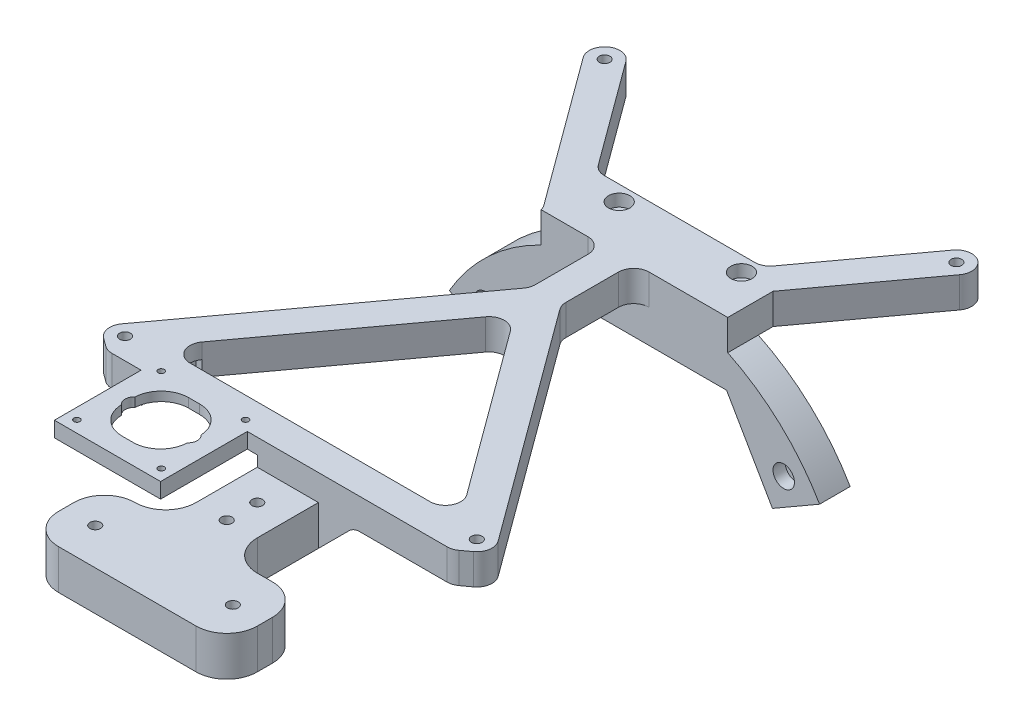
SolidWorks part; units mm, degrees
ref_plane "Plan de face" through (0, 0, 0) normal (0, 0, 1) x (1, 0, 0)
ref_plane "Plan de dessus" through (0, 0, 0) normal (0, 1, 0) x (1, 0, 0)
ref_plane "Plan de droite" through (0, 0, 0) normal (1, 0, 0) x (0, 0, -1)
sketch "Esquisse1" plane through (0, 0, 0) normal (0, 0, 1) x (1, 0, 0)
  line L0 (-30.13, 52.18) -> (30.13, 52.18)
  line L1 (30.13, 52.18) -> (45.13, 26.1992)
  line L2 (45.13, 26.1992) -> (60.5596, 35.1075)
  line L3 (-30.13, 52.18) -> (-45.13, 26.1992)
  line L4 (-45.13, 26.1992) -> (-60.5596, 35.1075)
  line L5 (-30.5123, 63) -> (30.5123, 63)
  circle A0 centre (0, 0) radius 70 construction
  arc A1 (-60.5596, 35.1075) -> (-30.5123, 63) centre (0, 0) cw
  arc A2 (60.5596, 35.1075) -> (30.5123, 63) centre (0, 0) ccw
  point P5 (0, 52.18)
  point P12 (0, 63)
  dimension "D1" = 140
  dimension "D2" = 120
  dimension "D3" = 30
  dimension "D4" = 60.26
  dimension "D5" = 61.0246
  dimension "D6" = 10.82
extrude "Boss.-Extru.1" add sketch "Esquisse1" along normal blind 10
sketch "Esquisse2" plane through (0, 63, 0) normal (0, 1, 0) x (1, 0, 0)
  line L0 (-30.5123, -10) -> (-30.5123, 0) construction
  line L1 (30.5123, -10) -> (-30.5123, -10)
  line L2 (30.5123, -10) -> (30.5123, 10)
  line L3 (30.5123, 10) -> (-30.5123, 10)
  line L4 (-30.5123, -10) -> (-30.5123, 10)
  line L5 (30.5123, 0) -> (-30.5123, 0) construction
  dimension "D1" = 10
extrude "Boss.-Extru.2" add sketch "Esquisse2" along normal blind 10
sketch "Esquisse5" plane through (0, 0, 10) normal (0, 0, 1) x (1, 0, 0)
  line L0 (-41.2992, 32.8344) -> (-56.3527, 41.5256) construction
  line L1 (-45.13, 26.1992) -> (-30.13, 52.18) construction
  line L2 (41.2992, 32.8344) -> (56.3527, 41.5256) construction
  line L3 (30.13, 52.18) -> (45.13, 26.1992) construction
  line L4 (-48.8259, 37.18) -> (48.8259, 37.18) construction
  line L5 (0, 52.18) -> (0, 37.18) construction
  line L6 (-30.13, 52.18) -> (30.13, 52.18) construction
  line L7 (-60.5596, 35.1075) -> (-45.13, 26.1992) construction
  line L8 (45.13, 26.1992) -> (60.5596, 35.1075) construction
  arc A0 (-30.5123, 63) -> (-60.5596, 35.1075) centre (0, 0) ccw construction
  arc A1 (60.5596, 35.1075) -> (30.5123, 63) centre (0, 0) ccw construction
  circle A2 centre (-48.8259, 37.18) radius 1.75
  circle A3 centre (48.8259, 37.18) radius 1.75
  dimension "D2" = 3.5
  dimension "D1" = 15
extrude "Enlèv. mat.-Extru.3" cut sketch "Esquisse5" against normal up to next
sketch "Esquisse3" plane through (0, 73, 0) normal (0, 1, 0) x (1, 0, 0)
  line L0 (30.5123, 0) -> (-30.5123, 0) construction
  line L1 (30.5123, -10) -> (30.5123, 10) construction
  line L2 (-30.5123, 10) -> (-30.5123, -10) construction
  line L3 (0, 0) -> (0, 10) construction
  line L4 (30.5123, 10) -> (-30.5123, 10) construction
  line L5 (20, 5) -> (-20, 5) construction
  circle A0 centre (20, 5) radius 1.75
  circle A1 centre (-20, 5) radius 1.75
  point P14 (0, 5)
  point P15 (0, 5)
  dimension "D1" = 3.5
  dimension "D2" = 20
extrude "Enlèv. mat.-Extru.1" cut sketch "Esquisse3" against normal up to next
sketch "Esquisse4" plane through (0, 73, 0) normal (0, 1, 0) x (1, 0, 0)
  circle A0 centre (20, 5) radius 3.5
  circle A1 centre (-20, 5) radius 3.5
  dimension "D1" = 7
extrude "Enlèv. mat.-Extru.2" cut sketch "Esquisse4" against normal blind 4
sketch "Esquisse6" plane through (0, 0, 10) normal (0, 0, 1) x (1, 0, 0)
  circle A0 centre (-48.8259, 37.18) radius 3.5
  circle A1 centre (48.8259, 37.18) radius 3.5
  dimension "D1" = 7
extrude "Enlèv. mat.-Extru.4" cut sketch "Esquisse6" against normal blind 4
sketch "Esquisse7" plane through (0, 73, 0) normal (0, 1, 0) x (1, 0, 0)
  line L0 (0, -10) -> (0, 10) construction
  line L1 (-30.5123, -10) -> (30.5123, -10) construction
  line L2 (30.5123, 10) -> (-30.5123, 10) construction
  line L3 (-62.77, -113.9) -> (52.31, 43) construction
  line L4 (52.31, -113.9) -> (-62.77, 43) construction
  line L5 (-10.23, -10) -> (-10.23, -33.8129)
  line L7 (59.2989, -114.9746) -> (51.2354, -120.8889)
  line L8 (51.2354, -120.8889) -> (-5.23, -43.9041)
  line L9 (-5.23, -43.9041) -> (-61.6954, -120.8889)
  line L10 (-61.6954, -120.8889) -> (-69.7589, -114.9746)
  line L12 (-0.23, -33.8129) -> (-0.23, -10)
  line L13 (52.31, -113.9) -> (55.2672, -117.9318) construction
  line L14 (-62.77, -113.9) -> (-65.7272, -117.9318) construction
  line L16 (30.5123, 4.8269) -> (59.2989, 44.0746)
  line L17 (59.2989, 44.0746) -> (51.2354, 49.9889)
  line L18 (51.2354, 49.9889) -> (21.9051, 10)
  line L19 (52.31, 43) -> (55.2672, 47.0318) construction
  line L20 (-32.3651, 10) -> (-61.6954, 49.9889)
  line L21 (-61.6954, 49.9889) -> (-69.7589, 44.0746)
  line L22 (-69.7589, 44.0746) -> (-30.5123, -9.4342)
  line L23 (-30.5123, 10) -> (-30.5123, -10) construction
  line L24 (-30.5123, -9.4342) -> (-30.5123, 10)
  line L25 (-30.5123, 10) -> (-32.3651, 10)
  line L26 (-62.77, 43) -> (-65.7272, 47.0318) construction
  line L27 (-10.23, -10) -> (-0.23, -10)
  line L28 (30.5123, 10) -> (30.5123, 4.8269)
  line L29 (30.5123, -10) -> (30.5123, 10) construction
  line L30 (30.5123, 10) -> (21.9051, 10)
  line L31 (59.2989, -114.9746) -> (-0.23, -33.8129)
  line L32 (-10.23, -33.8129) -> (-69.7589, -114.9746)
  circle A0 centre (52.31, -113.9) radius 1.75
  circle A1 centre (-62.77, -113.9) radius 1.75
  circle A2 centre (-62.77, 43) radius 1.75
  circle A3 centre (52.31, 43) radius 1.75
  point P10 (-5.23, -35.45)
  point P11 (-5.23, -35.45)
  dimension "D5" = 3.5
  dimension "D1" = 156.9
  dimension "D2" = 115.08
  dimension "D3" = 5.23
  dimension "D4" = 5
  dimension "D6" = 10
  dimension "D8" = 33
extrude "Boss.-Extru.3" add sketch "Esquisse7" against normal up to surface (10 mm away) up to face at (20, 63, -3.25)
sketch "Esquisse8" plane through (0, 73, 0) normal (0, 1, 0) x (1, 0, 0)
  line L0 (51.2354, -120.8889) -> (43.9008, -110.8889)
  line L1 (-5.23, -43.9041) -> (51.2354, -120.8889) construction
  line L2 (43.9008, -110.8889) -> (-54.3608, -110.8889)
  line L3 (-61.6954, -120.8889) -> (-5.23, -43.9041) construction
  line L4 (-54.3608, -110.8889) -> (-61.6954, -120.8889)
  line L5 (-61.6954, -120.8889) -> (51.2354, -120.8889)
  dimension "D1" = 10
extrude "Boss.-Extru.4" add sketch "Esquisse8" against normal up to surface (10 mm away) up to face at (-5.23, 63, 67.0286)
ref_plane "Plan1" through (0, 64.5, 0) normal (0, -1, 0) x (-1, 0, 0)
sketch "Esquisse9" plane through (0, 63, 0) normal (0, -1, 0) x (-1, 0, 0)
  circle A0 centre (-52.31, -113.9) radius 3.5
  circle A1 centre (62.77, -113.9) radius 3.5
  circle A2 centre (62.77, 43) radius 3.5
  circle A3 centre (-52.31, 43) radius 3.5
  dimension "D1" = 7
extrude "Enlèv. mat.-Extru.5" cut sketch "Esquisse9" against normal blind 3
sketch "Esquisse10" plane through (0, 64.5, 0) normal (0, -1, 0) x (-1, 0, 0)
  line L0 (54.3608, -110.8889) -> (-43.9008, -110.8889) construction
  line L1 (32.5, -175.8889) -> (-32.5, -175.8889)
  line L5 (-51.2354, -120.8889) -> (61.6954, -120.8889) construction
  line L6 (32.5, -150.8889) -> (12.5, -150.8889)
  line L7 (12.5, -150.8889) -> (12.5, -110.8889)
  line L8 (12.5, -110.8889) -> (-7.5, -110.8889)
  line L9 (-7.5, -110.8889) -> (-7.5, -150.8889)
  line L10 (-7.5, -150.8889) -> (-32.5, -150.8889)
  line L11 (32.5, -175.8889) -> (32.5, -150.8889)
  line L12 (-32.5, -175.8889) -> (-32.5, -150.8889)
  dimension "D3" = 49.1954
  dimension "D1" = 65
  dimension "D2" = 55
  dimension "D4" = 20
  dimension "D5" = 25
  dimension "D6" = 30
extrude "Boss.-Extru.5" add sketch "Esquisse10" along normal blind 13
sketch "Esquisse11" plane through (0, 51.5, 0) normal (0, -1, 0) x (1, 0, 0)
  line L0 (-22.5, 163.8889) -> (22.5, 163.8889) construction
  line L1 (32.5, 175.8889) -> (-32.5, 175.8889) construction
  circle A0 centre (-22.5, 163.8889) radius 1.75
  circle A1 centre (22.5, 163.8889) radius 1.75
  point P4 (0, 163.8889)
  point P7 (0, 175.8889)
  dimension "D2" = 3.5
  dimension "D1" = 45
  dimension "D3" = 12
extrude "Enlèv. mat.-Extru.6" cut sketch "Esquisse11" against normal up to next
sketch "Esquisse14" plane through (0, 51.5, 0) normal (0, -1, 0) x (1, 0, 0)
  line L0 (-12.5, 110.8889) -> (7.5, 110.8889) construction
  line L3 (-2.5, 140.8889) -> (-2.5, 130.8889) construction
  circle A0 centre (-2.5, 140.8889) radius 1.75
  circle A1 centre (-2.5, 130.8889) radius 1.75
  dimension "D1" = 3.5
  dimension "D2" = 10
  dimension "D3" = 20
extrude "Enlèv. mat.-Extru.9" cut sketch "Esquisse14" against normal up to next
fillet "Congé2" radius 5 18 edges at (-54.3608, 68, 110.8889) (43.9008, 68, 110.8889) (51.2354, 68, 120.8889) (-5.23, 68, 43.9041) (21.9051, 68, -10) (-32.3651, 68, -10) (-10.23, 68, 10) (59.2989, 68, -44.0746) (51.2354, 68, -49.9889) (-61.6954, 68, -49.9889) (-69.7589, 68, -44.0746) (-30.5123, 68, 9.4342) (-0.23, 68, 10) (-61.6954, 68, 120.8889) (-69.7589, 68, 114.9746) (59.2989, 68, 114.9746) (-10.23, 68, 33.8129) (-0.23, 68, 33.8129)
fillet "Congé1" radius 10 6 edges at (32.5, 58, 175.8889) (-32.5, 58, 175.8889) (32.5, 58, 150.8889) (-32.5, 58, 150.8889) (-12.5, 58, 150.8889) (7.5, 58, 150.8889)
sketch "Esquisse12" plane through (0, 51.5, 0) normal (0, -1, 0) x (1, 0, 0)
  circle A0 centre (-22.5, 163.8889) radius 3.5
  circle A1 centre (22.5, 163.8889) radius 3.5
  dimension "D1" = 7
extrude "Enlèv. mat.-Extru.7" cut sketch "Esquisse12" against normal blind 4.75
sketch "Esquisse15" plane through (0, 51.5, 0) normal (0, -1, 0) x (1, 0, 0)
  circle A0 centre (-2.5, 140.8889) radius 3.5
  circle A1 centre (-2.5, 130.8889) radius 3.5
  dimension "D1" = 7
extrude "Enlèv. mat.-Extru.10" cut sketch "Esquisse15" against normal offset from surface (7 mm away) 6 up to face at (-2.5, 64.5, 139.1389)
sketch "Esquisse16" plane through (0, 63, 0) normal (0, -1, 0) x (1, 0, 0)
  line L0 (-12.5, 120.8889) -> (-60.0583, 120.8889) construction
  line L1 (-12.5, 120.8889) -> (-50.5, 120.8889)
  line L2 (-12.5, 120.8889) -> (-12.5, 110.8889)
  line L4 (-50.5, 120.8889) -> (-50.5, 102.9318)
  line L5 (-12.5, 120.8889) -> (-12.5, 110.8889) construction
  line L7 (-50.5, 102.9318) -> (-48.5245, 102.9318)
  line L8 (-12.5, 110.8889) -> (-44.4927, 110.8889)
  arc A0 (-44.4927, 110.8889) -> (-48.5245, 102.9318) centre (-44.4927, 105.8889) ccw
  dimension "D1" = 38
extrude "Enlèv. mat.-Extru.11" cut sketch "Esquisse16" against normal blind 5
sketch "Esquisse19" plane through (0, 68, 0) normal (0, -1, 0) x (1, 0, 0)
  line L0 (-50.5, 120.8889) -> (-50.5, 149.2539)
  line L1 (-15.77, 120.8889) -> (-15.77, 149.2539)
  line L2 (-12.5, 120.8889) -> (-50.5, 120.8889) construction
  line L3 (-15.77, 149.2539) -> (-50.5, 149.2539)
  line L5 (-43.9253, 142.6792) -> (-22.3447, 142.6792)
  line L7 (-43.9253, 120.8889) -> (-50.5, 120.8889)
  line L8 (-22.3447, 120.8889) -> (-15.77, 120.8889)
  line L9 (-43.9253, 142.6792) -> (-43.9253, 149.2539) construction
  line L10 (-43.9253, 120.8889) -> (-43.9253, 129.4429)
  line L11 (-43.9253, 142.6792) -> (-43.9253, 133.915)
  line L12 (-22.3447, 120.8889) -> (-22.3447, 129.4429)
  line L13 (-22.3447, 133.915) -> (-22.3447, 142.6792)
  line L14 (-41.9253, 131.6789) -> (-44.9253, 131.6789) construction
  line L15 (-24.3447, 131.6789) -> (-21.3447, 131.6789) construction
  arc A2 (-43.9253, 133.915) -> (-43.9253, 129.4429) centre (-41.9253, 131.6789) ccw
  arc A3 (-22.3447, 133.915) -> (-22.3447, 129.4429) centre (-24.3447, 131.6789) cw
  dimension "D2" = 2
  dimension "D4" = 3
  dimension "D1" = 28.365
  dimension "D3" = 10.79
  dimension "D5" = 6.5747
extrude "Boss.-Extru.6" add sketch "Esquisse19" against normal up to surface (5 mm away) up to face at (-5.23, 73, 87.8129)
sketch "Esquisse17" plane through (0, 68, 0) normal (0, -1, 0) x (-1, 0, 0)
  line L0 (12.5, -110.8889) -> (12.5, -120.8889) construction
  line L1 (12.5, -120.8889) -> (15.77, -120.8889) construction
  line L2 (46.9253, -117.8889) -> (19.3447, -117.8889) construction
  line L3 (46.9253, -117.8889) -> (46.9253, -145.4695) construction
  circle A0 centre (46.9253, -117.8889) radius 1
  circle A1 centre (19.3447, -117.8889) radius 1
  circle A2 centre (46.9253, -145.4695) radius 1
  circle A3 centre (19.3447, -145.4695) radius 1
  dimension "D1" = 2
  dimension "D2" = 27.5806
  dimension "D3" = 6.8447
  dimension "D4" = 3
extrude "Enlèv. mat.-Extru.14" cut sketch "Esquisse17" against normal up to next
sketch "Esquisse18" plane through (0, 68, 0) normal (0, -1, 0) x (-1, 0, 0)
  line L0 (12.5, -120.8889) -> (15.77, -120.8889) construction
  line L2 (43.9253, -120.8889) -> (43.9253, -115.8889)
  line L3 (43.9253, -115.8889) -> (22.3447, -115.8889)
  line L4 (22.3447, -120.8889) -> (22.3447, -115.8889)
  line L5 (22.3447, -120.8889) -> (43.9253, -120.8889) construction
  line L6 (43.9253, -120.8889) -> (43.9253, -129.4429) construction
  line L7 (22.3447, -129.4429) -> (22.3447, -120.8889) construction
  line L9 (43.9253, -120.8889) -> (48.9253, -120.8889)
  line L11 (43.9253, -142.6792) -> (48.9253, -142.6792)
  line L12 (48.9253, -120.8889) -> (48.9253, -142.6792)
  line L13 (22.3447, -120.8889) -> (17.3447, -120.8889)
  line L15 (22.3447, -125.6792) -> (17.3447, -125.6792)
  line L16 (17.3447, -120.8889) -> (17.3447, -125.6792)
  line L18 (43.9253, -142.6792) -> (43.9253, -147.6792)
  line L19 (43.9253, -147.6792) -> (22.3447, -147.6792)
  line L20 (22.3447, -125.6792) -> (22.3447, -147.6792)
  dimension "D3" = 5
extrude "Enlèv. mat.-Extru.15" cut sketch "Esquisse18" against normal blind 2
chamfer "Chanfrein1" distance 11.5 angle 45 1 edges at (7.5, 63, 115.8889)
fillet "Congé3" radius 5 1 edges at (19, 63, 115.8889)
fillet "Congé4" radius 9 4 edges at (-43.9253, 71.5, 142.6792) (-43.9253, 71.5, 120.8889) (-22.3447, 71.5, 120.8889) (-22.3447, 71.5, 142.6792)
